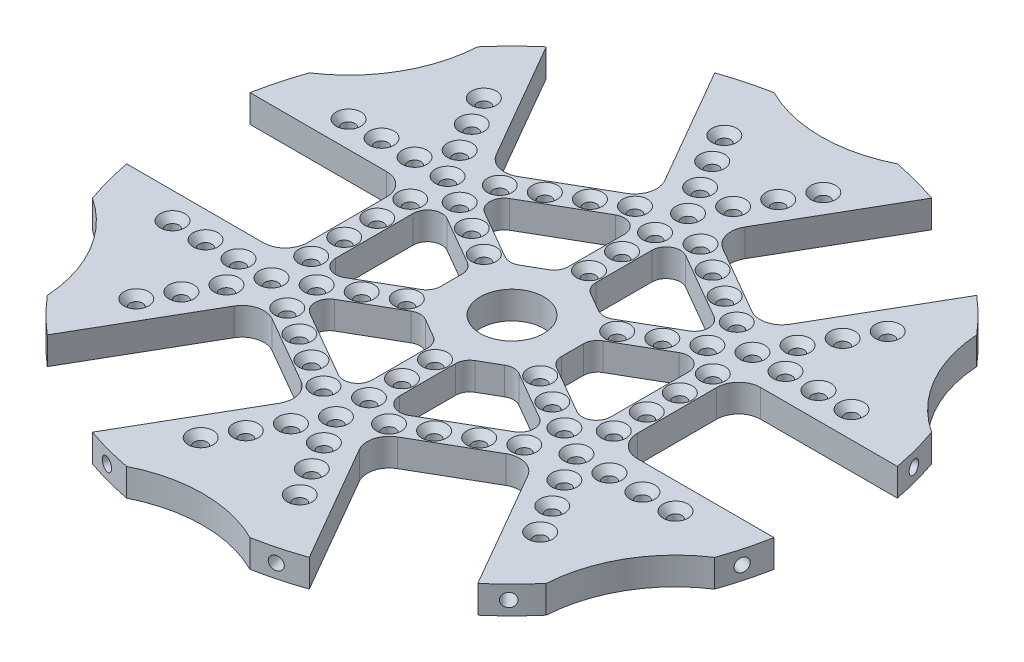
SolidWorks part; units mm, degrees
material "6061-T6 (SS)"
ref_plane "Front Plane" through (0, 0, 0) normal (0, 0, 1) x (1, 0, 0)
ref_plane "Top Plane" through (0, 0, 0) normal (0, 1, 0) x (1, 0, 0)
ref_plane "Right Plane" through (0, 0, 0) normal (1, 0, 0) x (0, 0, -1)
sketch "Sketch1" plane through (0, 0, 0) normal (0, 1, 0) x (1, 0, 0)
  line L0 (0, -76.2) -> (0, 94.2288) construction
  line L1 (0, 0) -> (-65.9911, 38.1) construction
  line L2 (0, 0) -> (-19.6891, 73.4809) construction
  line L3 (-14.2385, 74.7286) -> (0, 50.0669)
  line L4 (-25.0335, 71.8361) -> (0, 28.4769)
  line L5 (0, 50.0669) -> (0, 33.9762)
  line L6 (0, 0) -> (-3.175, 0)
  line L7 (0, 0) -> (0, 33.9762)
  line L8 (0, 33.9762) -> (-3.175, 33.9762)
  line L9 (-3.175, 0) -> (-3.175, 33.9762)
  arc A1 (-25.0335, 71.8361) -> (-19.6891, 73.4809) centre (0, 0) cw
  arc A3 (-14.2385, 74.7286) -> (-19.6891, 73.4809) centre (0, 0) ccw
  circle A4 centre (0, 0) radius 76.073
  dimension "D6" = 152.146
  dimension "D7" = 76.073
  dimension "D8" = 76.073
  dimension "D1" = 15
  dimension "D2" = 60
  dimension "D3" = 30
  dimension "D4" = 10.795
  dimension "D5" = 3.175
extrude "Boss-Extrude1" add sketch "Sketch1" along normal blind 6.35 contours L3 A3 A1 L4 L8 L5 | L7 L6 L9 L8 region at (-10.2892, 0, -56.275)
mirror "Mirror1" of "Boss-Extrude1"
sketch "Sketch2" plane through (0, 0, 0) normal (0, 0, 1) x (1, 0, 0)
  line L0 (0, 6.35) -> (0, 0)
  line L1 (3.175, 6.35) -> (-3.175, 6.35) construction
pattern_circular "CirPattern9" count 6 over 360 about axis through (0, 6.35, 0) along (0, -1, 0) of bodies 102
ref_plane "Plane1" through (3.175, 6.35, 0) normal (0, 0, -1) x (-1, 0, 0)
sketch "Sketch4" plane through (0, 6.35, 0) normal (0, 1, 0) x (1, 0, 0)
  line L1 (0, 16.1312) -> (-13.97, 8.0656)
  line L2 (-13.97, 8.0656) -> (-13.97, -8.0656)
  line L3 (-13.97, -8.0656) -> (0, -16.1312)
  line L4 (0, -16.1312) -> (13.97, -8.0656)
  line L5 (13.97, -8.0656) -> (13.97, 8.0656)
  line L6 (13.97, 8.0656) -> (0, 16.1312)
  circle A0 centre (0, 0) radius 13.97 construction
  dimension "D1" = 27.94
extrude "Boss-Extrude2" add sketch "Sketch4" against normal blind 6.35
sketch "Sketch5" plane through (0, 6.35, 0) normal (0, 1, 0) x (1, 0, 0)
  circle A0 centre (0, 0) radius 6.35
extrude "Cut-Extrude1" cut sketch "Sketch5" against normal blind 6.35
sketch "Sketch6" plane through (0, 6.35, 0) normal (0, 1, 0) x (1, 0, 0)
  line L0 (-28.7945, 20.0372) -> (-2.9555, 34.9554)
  line L1 (-28.7945, 20.0372) -> (-31.9695, 25.5365)
  line L2 (-2.9555, 34.9554) -> (-6.1305, 40.4547)
  line L3 (-31.9695, 25.5365) -> (-6.1305, 40.4547)
  point P0 (-15.875, 27.4963)
  dimension "D1" = 6.35
  dimension "D2" = 31.75
extrude "Boss-Extrude3" add sketch "Sketch6" against normal blind 6.35
pattern_circular "CirPattern10" count 6 every 60 about axis through (0, 6.35, 0) along (0, 1, 0) of "Boss-Extrude3"
ref_plane "Plane4" through (0, 3.175, 0) normal (0, 1, 0) x (1, 0, 0)
fillet "Fillet6" radius 5.08 12 edges at (38.1, 3.175, 14.2385) (38.1, 3.175, -14.2385) (31.3809, 3.175, 25.8763) (6.7191, 3.175, 40.1148) (-6.7191, 3.175, 40.1148) (-31.3809, 3.175, 25.8763) (-38.1, 3.175, 14.2385) (-38.1, 3.175, -14.2385) (-31.3809, 3.175, -25.8763) (-6.7191, 3.175, -40.1148) (31.3809, 3.175, -25.8763) (6.7191, 3.175, -40.1148)
sketch "Sketch46" plane through (0, 6.35, 0) normal (0, 1, 0) x (1, 0, 0)
  line L0 (3.175, -34.8287) -> (3.5441, -34.6155)
  line L1 (28.2059, -20.3771) -> (3.5441, -34.6155) construction
  line L2 (3.5441, -34.6155) -> (3.175, -33.9762)
  line L3 (10.795, -9.8987) -> (27.8367, -19.7377) construction
  line L4 (3.5441, -34.6155) -> (3.175, -33.9762)
  line L5 (3.5441, -34.6155) -> (3.175, -33.9762) construction
  line L6 (3.175, -33.9762) -> (3.175, -34.8287)
  line L7 (3.175, -33.9762) -> (3.5441, -34.6155)
  line L8 (0, -3.4925) -> (0, 3.4925) construction
  line L9 (-3.5441, -34.6155) -> (-3.175, -33.9762)
  line L10 (-3.175, -34.8287) -> (-3.5441, -34.6155)
  line L11 (-3.175, -33.9762) -> (-3.175, -34.8287)
  line L12 (-31.0117, -14.2385) -> (-31.75, -14.6647)
  line L13 (-31.75, -14.2385) -> (-31.0117, -14.2385)
  line L14 (-31.75, -14.6647) -> (-31.75, -14.2385)
  line L15 (-28.2059, -20.3771) -> (-27.8367, -19.7377)
  line L16 (-27.8367, -19.7377) -> (-28.575, -20.164)
  line L17 (-28.575, -20.164) -> (-28.2059, -20.3771)
  line L18 (-27.8367, 19.7377) -> (-28.575, 20.164)
  line L19 (-28.2059, 20.3771) -> (-27.8367, 19.7377)
  line L20 (-28.575, 20.164) -> (-28.2059, 20.3771)
  line L21 (-31.75, 14.2385) -> (-31.0117, 14.2385)
  line L22 (-31.0117, 14.2385) -> (-31.75, 14.6647)
  line L23 (-31.75, 14.6647) -> (-31.75, 14.2385)
  line L24 (3.175, 33.9762) -> (3.175, 34.8287)
  line L25 (3.5441, 34.6155) -> (3.175, 33.9762)
  line L26 (3.175, 34.8287) -> (3.5441, 34.6155)
  line L27 (-3.5441, 34.6155) -> (-3.175, 33.9762)
  line L28 (-3.175, 33.9762) -> (-3.175, 34.8287)
  line L29 (-3.175, 34.8287) -> (-3.5441, 34.6155)
  line L30 (31.0117, 14.2385) -> (31.75, 14.6647)
  line L31 (31.75, 14.2385) -> (31.0117, 14.2385)
  line L32 (31.75, 14.6647) -> (31.75, 14.2385)
  line L33 (28.2059, 20.3771) -> (27.8367, 19.7377)
  line L34 (27.8367, 19.7377) -> (28.575, 20.164)
  line L35 (28.575, 20.164) -> (28.2059, 20.3771)
  line L36 (27.8367, -19.7377) -> (28.575, -20.164)
  line L37 (28.2059, -20.3771) -> (27.8367, -19.7377)
  line L38 (28.575, -20.164) -> (28.2059, -20.3771)
  line L39 (31.75, -14.2385) -> (31.0117, -14.2385)
  line L40 (31.0117, -14.2385) -> (31.75, -14.6647)
  line L41 (31.75, -14.6647) -> (31.75, -14.2385)
  point P6 (3.4674, -34.4826)
  point P7 (3.5507, -34.6269)
  point P13 (3.5452, -34.6175)
  point P49 (0, 0)
  dimension "D1" = 6
hole_wizard "CSK for #4 Flat Head Machine Screw1" positions "Sketch22" profile "Sketch23" countersink size "#4" standard "ANSI Inch"
sketch "Sketch22" plane through (0, 6.35, 0) normal (0, 1, 0) x (1, 0, 0)
  circle A0 centre (0, 0) radius 10.16
  point P2 (0, 17.78)
  point P4 (0, 25.4)
  point P6 (0, 33.02)
  point P8 (0, 40.64)
  dimension "D2" = 17.78
  dimension "D3" = 25.4
  dimension "D4" = 33.02
  dimension "D5" = 40.64
sketch "Sketch23" plane through (0, 6.35, -17.78) normal (1, 0, 0) x (0, 0, 1)
  line L0 (0, 0) -> (0, 8.5052)
  line L1 (0, 8.5052) -> (1.4732, 7.62)
  line L2 (1.4732, 7.62) -> (1.4732, 1.5925)
  line L3 (1.4732, 1.5925) -> (2.8575, 0)
  line L5 (2.8575, 0) -> (0, 0)
  line L6 (-1.4732, 1.5925) -> (-2.8575, 0) construction
  line L10 (0, 8.5052) -> (-1.4732, 7.62) construction
  line L11 (0, -6.35) -> (0, 107.95) construction
  dimension "Hole Dia." = 2.9464
  dimension "Hole Depth" = 7.62
  dimension "Near C'Sink Dia." = 5.715
  dimension "Near C'Sink Angle" = 82
  dimension "Drill Angle" = 118
pattern_circular "CirPattern11" count 6 every 60 about axis through (0, 6.35, 0) along (0, 1, 0) of "CSK for #4 Flat Head Machine Screw1"
hole_wizard "CSK for #4 Flat Head Machine Screw2" positions "Sketch25" profile "Sketch26" countersink size "#4" standard "ANSI Inch"
sketch "Sketch25" plane through (0, 6.35, 0) normal (0, 1, 0) x (1, 0, 0)
  line L0 (-19.6891, -73.4809) -> (-4.1148, -82.561) construction
  line L3 (19.6891, -73.4809) -> (0, -40.64)
  line L4 (0, -40.64) -> (-19.6891, -73.4809)
  line L5 (-35.1953, -20.32) -> (-77.4452, -20.32)
  arc A0 (-25.0335, -71.8361) -> (-14.2385, -74.7286) centre (0, 0) ccw construction
  arc A1 (14.2385, -74.7286) -> (25.0335, -71.8361) centre (0, 0) ccw construction
  point P25 (-42.8153, -20.32)
  point P27 (-50.4353, -20.32)
  point P32 (-58.0553, -20.32)
  dimension "D1" = 7.62
  dimension "D2" = 7.62
  dimension "D3" = 7.62
sketch "Sketch26" plane through (-58.0553, 6.35, 20.32) normal (1, 0, 0) x (0, 0, 1)
  line L0 (0, 0) -> (0, 8.5052)
  line L1 (0, 8.5052) -> (1.4732, 7.62)
  line L2 (1.4732, 7.62) -> (1.4732, 1.5925)
  line L3 (1.4732, 1.5925) -> (2.8575, 0)
  line L5 (2.8575, 0) -> (0, 0)
  line L6 (-1.4732, 1.5925) -> (-2.8575, 0) construction
  line L10 (0, 8.5052) -> (-1.4732, 7.62) construction
  line L11 (0, -6.35) -> (0, 107.95) construction
  dimension "Hole Dia." = 2.9464
  dimension "Hole Depth" = 7.62
  dimension "Near C'Sink Dia." = 5.715
  dimension "Near C'Sink Angle" = 82
  dimension "Drill Angle" = 118
sketch "Sketch27" plane through (0, 6.35, 0) normal (0, 1, 0) x (1, 0, 0)
  line L0 (0, 0) -> (0, -79.3578)
mirror "Mirror2" about plane through (0, 0, 0) normal (1, 0, 0) of "CSK for #4 Flat Head Machine Screw2"
pattern_circular "CirPattern12" count 6 over 360 about axis through (0, 6.35, 0) along (0, 1, 0) of "CSK for #4 Flat Head Machine Screw2", "Mirror2"
hole_wizard "CSK for #4 Flat Head Machine Screw3" positions "Sketch28" profile "Sketch29" countersink size "#4" standard "ANSI Inch"
sketch "Sketch28" plane through (0, 6.35, 0) normal (0, 1, 0) x (1, 0, 0)
  line L0 (3.2873, 38.43) -> (31.6799, 22.0375)
  line L3 (26.9815, 28.4163) -> (11.1185, 37.5748) construction
  line L4 (18.2785, 29.7748) -> (19.866, 32.5244)
  line L7 (18.2785, 29.7748) -> (16.691, 27.0252)
  line L8 (3.5441, 34.6155) -> (28.2059, 20.3771) construction
  line L11 (0, 0) -> (0, 68.0291)
  line L12 (0, 68.0291) -> (0, 0)
  line L14 (0, 0) -> (40.501, 70.1499)
  point P0 (27.3612, 24.5309)
  point P2 (20.7621, 28.3409)
  point P4 (14.1629, 32.1509)
  point P6 (7.5638, 35.9609)
  dimension "D1" = 30
  dimension "D2" = 3.81
  dimension "D3" = 11.43
  dimension "D4" = 3.81
  dimension "D5" = 11.43
sketch "Sketch29" plane through (27.3612, 6.35, -24.5309) normal (1, 0, 0) x (0, 0, 1)
  line L0 (0, 0) -> (0, 8.5052)
  line L1 (0, 8.5052) -> (1.4732, 7.62)
  line L2 (1.4732, 7.62) -> (1.4732, 1.5925)
  line L3 (1.4732, 1.5925) -> (2.8575, 0)
  line L5 (2.8575, 0) -> (0, 0)
  line L6 (-1.4732, 1.5925) -> (-2.8575, 0) construction
  line L10 (0, 8.5052) -> (-1.4732, 7.62) construction
  line L11 (0, -6.35) -> (0, 107.95) construction
  dimension "Hole Dia." = 2.9464
  dimension "Hole Depth" = 7.62
  dimension "Near C'Sink Dia." = 5.715
  dimension "Near C'Sink Angle" = 82
  dimension "Drill Angle" = 118
pattern_circular "CirPattern13" count 6 over 360 about axis through (0, 0, 0) along (0, 1, 0) of "CSK for #4 Flat Head Machine Screw3" reverse direction yes
sketch "Sketch30" plane through (0, 6.35, 0) normal (0, 1, 0) x (1, 0, 0)
  circle A0 centre (0, 0) radius 6.35
extrude "Boss-Extrude4" add sketch "Sketch30" against normal blind 6.35
hole_wizard "9/16 Clearance Hole1" positions "Sketch33" profile "Sketch35" hole size "9/16" standard "ANSI Inch" end condition through all
sketch "Sketch33" plane through (0, 6.35, 0) normal (0, 1, 0) x (1, 0, 0)
  point P0 (0, 0)
sketch "Sketch35" plane through (0, 6.35, 0) normal (1, 0, 0) x (0, 0, 1)
  line L0 (0, 0) -> (0, 6.35)
  line L1 (0, 6.35) -> (7.3419, 6.35)
  line L2 (7.3419, 6.35) -> (7.3419, 0)
  line L5 (7.3419, 0) -> (0, 0)
  line L11 (0, -6.35) -> (0, 107.95) construction
  dimension "Thru Hole Dia." = 14.6837
  dimension "Thru Hole Depth" = 6.35
sketch "Sketch41" plane through (0, 6.35, 0) normal (0, 1, 0) x (1, 0, 0)
  circle A0 centre (0, 0) radius 76.2
sketch "Sketch43" plane through (0, 6.35, 0) normal (0, 1, 0) x (1, 0, 0)
  circle A0 centre (73.79, -18.7251) radius 0.0712
ref_plane "Plane7" through (19.6891, 0, -73.4809) normal (0.2588, 0, -0.9659) x (0, -1, 0)
hole_wizard "Tapped Hole for #4-40 Helicoil2" positions "Sketch50" profile "Sketch51" tap size "#4-40" standard "Helicoil® Inch"
sketch "Sketch50" plane through (19.6891, 0, -73.4809) normal (0.2588, 0, -0.9659) x (0, -1, 0)
  line L3 (0, -5.5879) -> (0, 5.5879) construction
  point P0 (-3.175, -0.5277)
  point P13 (0, 0)
  point P14 (0, 0)
  dimension "D1" = 3.175
  dimension "D2" = 0.5277
sketch "Sketch51" plane through (20.1988, 3.175, -73.3443) normal (0, 1, 0) x (-0.9659, 0, -0.2588)
  line L0 (0, 0) -> (0, 10.8217)
  line L1 (0, 10.8217) -> (1.524, 9.906)
  line L2 (1.524, 9.906) -> (1.524, 0)
  line L5 (1.524, 0) -> (0, 0)
  line L10 (0, 10.8217) -> (-1.524, 9.906) construction
  line L11 (0, -6.35) -> (0, 107.95) construction
  dimension "Tap Drill Dia." = 3.048
  dimension "Tap Drill Depth" = 9.906
  dimension "Drill Angle" = 118
pattern_circular "CirPattern14" count 12 over 360 about axis through (0, 6.35, 0) along (0, 1, 0) of "Tapped Hole for #4-40 Helicoil2" reverse direction yes
sketch "Sketch52" plane through (0, 6.35, 0) normal (0, 1, 0) x (1, 0, 0)
  line L0 (-27.8367, -19.7377) -> (-28.575, -20.164)
  line L1 (-28.575, -20.164) -> (-28.2059, -20.3771)
  line L2 (-3.5441, -34.6155) -> (-28.2059, -20.3771) construction
  line L3 (-10.795, -9.8987) -> (-27.8367, -19.7377) construction
  line L4 (-27.8367, -19.7377) -> (-28.2059, -20.3771)
  line L5 (-3.175, -33.9762) -> (-3.5441, -34.6155)
  line L6 (-3.5441, -34.6155) -> (-3.175, -34.8287)
  line L7 (-3.175, -34.8287) -> (-3.175, -33.9762)
  line L8 (-31.0117, 14.2385) -> (-31.75, 14.6647)
  line L9 (-31.75, 14.6647) -> (-31.75, 14.2385)
  line L10 (-31.0117, 14.2385) -> (-31.75, 14.2385)
  line L11 (-31.75, -14.6647) -> (-31.0117, -14.2385)
  line L12 (-31.0117, -14.2385) -> (-31.75, -14.2385)
  line L13 (-31.75, -14.2385) -> (-31.75, -14.6647)
  line L14 (-3.175, 33.9762) -> (-3.175, 34.8287)
  line L15 (-3.175, 34.8287) -> (-3.5441, 34.6155)
  line L16 (-3.175, 33.9762) -> (-3.5441, 34.6155)
  line L17 (-28.575, 20.164) -> (-27.8367, 19.7377)
  line L18 (-27.8367, 19.7377) -> (-28.2059, 20.3771)
  line L19 (-28.2059, 20.3771) -> (-28.575, 20.164)
  line L20 (27.8367, 19.7377) -> (28.575, 20.164)
  line L21 (28.575, 20.164) -> (28.2059, 20.3771)
  line L22 (27.8367, 19.7377) -> (28.2059, 20.3771)
  line L23 (3.175, 34.8287) -> (3.175, 33.9762)
  line L24 (3.175, 33.9762) -> (3.5441, 34.6155)
  line L25 (3.5441, 34.6155) -> (3.175, 34.8287)
  line L26 (31.0117, -14.2385) -> (31.75, -14.6647)
  line L27 (31.75, -14.6647) -> (31.75, -14.2385)
  line L28 (31.0117, -14.2385) -> (31.75, -14.2385)
  line L29 (31.75, 14.6647) -> (31.0117, 14.2385)
  line L30 (31.0117, 14.2385) -> (31.75, 14.2385)
  line L31 (31.75, 14.2385) -> (31.75, 14.6647)
  line L32 (3.175, -33.9762) -> (3.175, -34.8287)
  line L33 (3.175, -34.8287) -> (3.5441, -34.6155)
  line L34 (3.175, -33.9762) -> (3.5441, -34.6155)
  line L35 (28.575, -20.164) -> (27.8367, -19.7377)
  line L36 (27.8367, -19.7377) -> (28.2059, -20.3771)
  line L37 (28.2059, -20.3771) -> (28.575, -20.164)
  line L38 (0, 0) -> (-3.175, -33.9762) construction
  line L39 (0, 0) -> (-31.0117, -14.2385) construction
  dimension "D2" = 34.1242
  dimension "D3" = 60
  dimension "D4" = 33.9762
  dimension "D1" = 6
extrude "Cut-Extrude4" cut sketch "Sketch52" against normal through all
sketch "Sketch53" plane through (0, 6.35, 0) normal (0, 1, 0) x (1, 0, 0)
  line L0 (-57.5977, 49.6952) -> (-43.3592, 25.0335)
  line L1 (-43.3592, 25.0335) -> (-71.8361, 25.0335)
  line L2 (0, 50.0669) -> (-14.2385, 74.7286)
  line L3 (14.2385, 74.7286) -> (0, 50.0669)
  line L4 (43.3592, 25.0335) -> (57.5977, 49.6952)
  line L5 (71.8361, 25.0335) -> (43.3592, 25.0335)
  line L6 (43.3592, -25.0335) -> (71.8361, -25.0335)
  line L7 (57.5977, -49.6952) -> (43.3592, -25.0335)
  line L8 (0, -50.0669) -> (14.2385, -74.7286)
  line L9 (-14.2385, -74.7286) -> (0, -50.0669)
  line L10 (-43.3592, -25.0335) -> (-57.5977, -49.6952)
  line L11 (-71.8361, -25.0335) -> (-43.3592, -25.0335)
  line L12 (0, 0) -> (-43.3592, 25.0335) construction
  arc A0 (-57.5977, 49.6952) -> (-71.8361, 25.0335) centre (-89.2932, 51.5535) cw
  arc A1 (14.2385, 74.7286) -> (-14.2385, 74.7286) centre (0, 103.1069) cw
  arc A2 (71.8361, 25.0335) -> (57.5977, 49.6952) centre (89.2932, 51.5535) cw
  arc A3 (57.5977, -49.6952) -> (71.8361, -25.0335) centre (89.2932, -51.5535) cw
  arc A4 (-14.2385, -74.7286) -> (14.2385, -74.7286) centre (0, -103.1069) cw
  arc A5 (-71.8361, -25.0335) -> (-57.5977, -49.6952) centre (-89.2932, -51.5535) cw
  point P8 (0, 0)
  dimension "D1" = 31.75
  dimension "D3" = 50.0669
  dimension "D2" = 6
extrude "Boss-Extrude5" add sketch "Sketch53" against normal up to surface (6.35 mm away) up to face at (0, 0, 7.3419)
fillet "Fillet7" radius 3.302 24 edges at (-10.795, 3.175, -9.8987) (-3.175, 3.175, -14.2981) (-28.575, 3.175, -20.164) (-3.175, 3.175, -34.8287) (3.175, 3.175, -34.8287) (3.175, 3.175, -14.2981) (10.795, 3.175, -9.8987) (28.575, 3.175, -20.164) (13.97, 3.175, 4.3994) (13.97, 3.175, -4.3994) (31.75, 3.175, -14.6647) (31.75, 3.175, 14.6647) (3.175, 3.175, 14.2981) (10.795, 3.175, 9.8987) (28.575, 3.175, 20.164) (3.175, 3.175, 34.8287) (-28.575, 3.175, 20.164) (-3.175, 3.175, 34.8287) (-10.795, 3.175, 9.8987) (-3.175, 3.175, 14.2981) (-31.75, 3.175, -14.6647) (-31.75, 3.175, 14.6647) (-13.97, 3.175, 4.3994) (-13.97, 3.175, -4.3994)
equation "\"anchor\"= .425"
equation "\"D4@Sketch1\"=\"anchor\""
equation "\"half arm\"= .125"
equation "\"D5@Sketch1\"=\"half arm\""
equation "\"strut\"= .25"
equation "\"D1@Sketch6\"=\"strut\""
